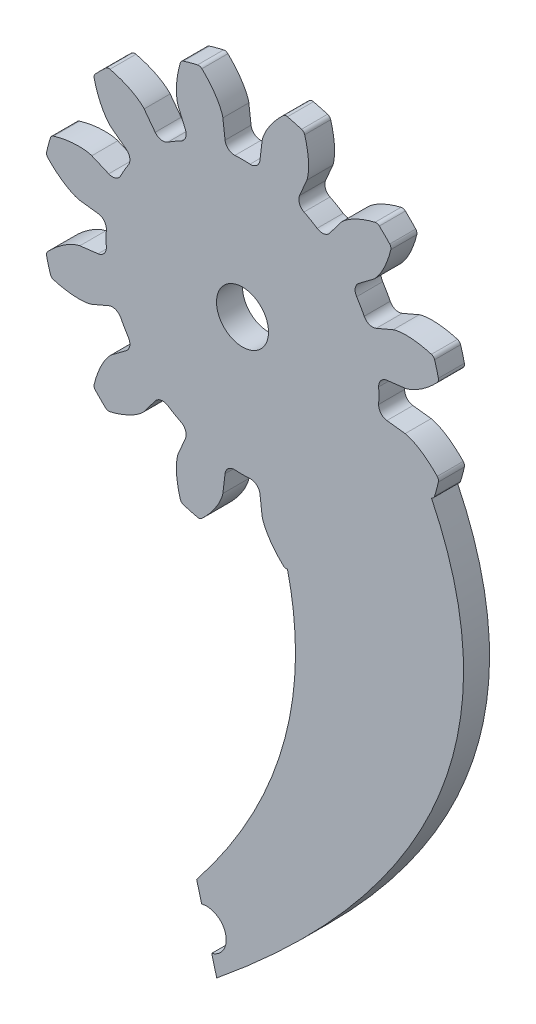
SolidWorks part; units mm, degrees
material "Alloy Steel"
ref_plane "Front" through (0, 0, 0) normal (0, 0, 1) x (1, 0, 0)
ref_plane "Top" through (0, 0, 0) normal (0, 1, 0) x (1, 0, 0)
ref_plane "Right" through (0, 0, 0) normal (1, 0, 0) x (0, 0, -1)
sketch "Sketch1" plane through (0, 0, 0) normal (0, 0, 1) x (1, 0, 0)
  circle A0 centre (0, 0) radius 15.4609
  dimension "OutsideDiameter" = 30.9217
extrude "Boss-Extrude1" add sketch "Sketch1" along normal blind 2
sketch "Sketch3" plane through (0, 0, 0) normal (0, 0, 1) x (1, 0, 0)
  line L0 (0, 0) -> (43.7181, 0) construction
  line L2 (0, 0) -> (-1.2574, 10.4157) construction
  line L3 (0, 0) -> (1.2574, 10.4157) construction
  line L4 (1.2574, 10.4157) -> (1.5105, 12.5127) construction
  line L5 (0, 0) -> (0, 61.276) construction
  line L6 (-1.2574, 10.4157) -> (-1.5105, 12.5127) construction
  circle A0 centre (0, 0) radius 15.4609 construction
  circle A1 centre (0, 0) radius 13.2522 construction
  circle A2 centre (0, 0) radius 12.6036 construction
  arc A3 (1.2574, 10.4157) -> (-1.2574, 10.4157) centre (0, 0) ccw construction
  arc A5 (5.6606, 16.7383) -> (-5.6606, 16.7383) centre (0, 0) ccw
  spline S0 degree 4 poles (-1.5105, 12.5127) (-1.5118, 12.5216) (-1.5159, 12.5465) (-1.526, 12.5932) (-1.5455, 12.6687) (-1.5751, 12.7638) (-1.6185, 12.8852) (-1.6764, 13.026) (-1.7469, 13.1782) (-1.831, 13.3407) (-1.9213, 13.5001) (-2.0172, 13.6562) (-2.118, 13.8091) (-2.2461, 13.9909) (-2.4081, 14.2041) (-2.6093, 14.4459) (-2.8511, 14.711) (-3.1116, 14.9707) (-3.3794, 15.2174) (-3.6624, 15.456) (-3.945, 15.6793) (-4.2506, 15.8995) (-4.5388, 16.0969) (-4.8743, 16.3046) (-5.1487, 16.4683) (-5.5233, 16.6694) (-5.7482, 16.7837) (-6.0156, 16.9122) (-6.1365, 16.9665) (-6.2108, 17) knots 0 0 0 0 0 0.005377 0.015084 0.028532 0.04661 0.064855 0.092111 0.119476 0.146842 0.174209 0.201575 0.228941 0.256307 0.307035 0.361767 0.4165 0.471232 0.525964 0.580697 0.635429 0.690161 0.744894 0.799626 0.854358 0.909091 0.954545 1 1 1 1 1 construction
  spline S1 degree 4 poles (-1.5105, 12.5127) (-1.5118, 12.5216) (-1.5159, 12.5465) (-1.526, 12.5932) (-1.5455, 12.6687) (-1.5751, 12.7638) (-1.6185, 12.8852) (-1.6764, 13.026) (-1.7469, 13.1782) (-1.831, 13.3407) (-1.9213, 13.5001) (-2.0172, 13.6562) (-2.118, 13.8091) (-2.2461, 13.9909) (-2.4081, 14.2041) (-2.6093, 14.4459) (-2.8511, 14.711) (-3.1116, 14.9707) (-3.3794, 15.2174) (-3.6624, 15.456) (-3.945, 15.6793) (-4.2506, 15.8995) (-4.5388, 16.0969) (-4.8743, 16.3046) (-5.1487, 16.4683) (-5.4421, 16.6258) (-5.5863, 16.7008) (-5.6606, 16.7383) knots 0 0 0 0 0 0.005377 0.015084 0.028532 0.04661 0.064855 0.092111 0.119476 0.146842 0.174209 0.201575 0.228941 0.256307 0.307035 0.361767 0.4165 0.471232 0.525964 0.580697 0.635429 0.690161 0.744894 0.799626 0.854358 0.909091 0.909091 0.909091 0.909091 0.909091
  spline S2 degree 4 poles (1.5105, 12.5127) (1.5118, 12.5216) (1.5159, 12.5465) (1.526, 12.5932) (1.5455, 12.6687) (1.5751, 12.7638) (1.6185, 12.8852) (1.6764, 13.026) (1.7469, 13.1782) (1.831, 13.3407) (1.9213, 13.5001) (2.0172, 13.6562) (2.118, 13.8091) (2.2461, 13.9909) (2.4081, 14.2041) (2.6093, 14.4459) (2.8511, 14.711) (3.1116, 14.9707) (3.3794, 15.2174) (3.6624, 15.456) (3.945, 15.6793) (4.2506, 15.8995) (4.5388, 16.0969) (4.8743, 16.3046) (5.1487, 16.4683) (5.5233, 16.6694) (5.7482, 16.7837) (6.0156, 16.9122) (6.1365, 16.9665) (6.2108, 17) knots 0 0 0 0 0 0.005377 0.015084 0.028532 0.04661 0.064855 0.092111 0.119476 0.146842 0.174209 0.201575 0.228941 0.256307 0.307035 0.361767 0.4165 0.471232 0.525964 0.580697 0.635429 0.690161 0.744894 0.799626 0.854358 0.909091 0.954545 1 1 1 1 1 construction
  spline S3 degree 4 poles (1.5105, 12.5127) (1.5118, 12.5216) (1.5159, 12.5465) (1.526, 12.5932) (1.5455, 12.6687) (1.5751, 12.7638) (1.6185, 12.8852) (1.6764, 13.026) (1.7469, 13.1782) (1.831, 13.3407) (1.9213, 13.5001) (2.0172, 13.6562) (2.118, 13.8091) (2.2461, 13.9909) (2.4081, 14.2041) (2.6093, 14.4459) (2.8511, 14.711) (3.1116, 14.9707) (3.3794, 15.2174) (3.6624, 15.456) (3.945, 15.6793) (4.2506, 15.8995) (4.5388, 16.0969) (4.8743, 16.3046) (5.1487, 16.4683) (5.4421, 16.6258) (5.5863, 16.7008) (5.6606, 16.7383) knots 0 0 0 0 0 0.005377 0.015084 0.028532 0.04661 0.064855 0.092111 0.119476 0.146842 0.174209 0.201575 0.228941 0.256307 0.307035 0.361767 0.4165 0.471232 0.525964 0.580697 0.635429 0.690161 0.744894 0.799626 0.854358 0.909091 0.909091 0.909091 0.909091 0.909091
  point P0 (0, 10.4913)
  dimension "OutsideDiameter" = 30.9217
  dimension "PitchCircle" = 26.5043
  dimension "BaseCircle" = 25.2071
  dimension "DedendumCircle" = 20.9826
sketch "DCLTBC" plane through (0, 0, 0) normal (0, 0, 1) x (1, 0, 0)
  line L0 (0, 0) -> (41.04, 0) construction
  line L1 (-1.2574, 10.4157) -> (-1.5105, 12.5127) construction
  line L2 (1.2574, 10.4157) -> (1.5105, 12.5127) construction
  line L3 (-1.2574, 10.4157) -> (-1.5105, 12.5127)
  line L4 (1.2574, 10.4157) -> (1.5105, 12.5127)
  line L5 (0, 0) -> (0, 104.9356) construction
  circle A0 centre (0, 0) radius 15.4609
  circle A1 centre (0, 0) radius 13.2522 construction
  circle A2 centre (0, 0) radius 12.6036 construction
  arc A3 (1.2574, 10.4157) -> (-1.2574, 10.4157) centre (0, 0) ccw construction
  arc A4 (1.2574, 10.4157) -> (-1.2574, 10.4157) centre (0, 0) ccw
  spline S0 degree 4 poles (-993.0276, -117.3129) (-18.3285, 8.2146) (-1.6428, 11.057) (-1.3485, 11.9079) (-1.5455, 12.6687) (-1.5751, 12.7638) (-1.6185, 12.8852) (-1.6764, 13.026) (-1.7469, 13.1782) (-1.831, 13.3407) (-1.9213, 13.5001) (-2.0172, 13.6562) (-2.118, 13.8091) (-2.2461, 13.9909) (-2.4081, 14.2041) (-2.6093, 14.4459) (-2.8511, 14.711) (-3.1116, 14.9707) (-3.3794, 15.2174) (-3.6624, 15.456) (-3.945, 15.6793) (-4.2506, 15.8995) (-4.5388, 16.0969) (-4.8743, 16.3046) (-6.0414, 17.0009) (-9.6339, 18.6454) (22.9818, 1.8118) (-898.4388, 467.1598) knots -0.423011 -0.423011 -0.423011 -0.423011 -0.423011 0.005377 0.015084 0.028532 0.04661 0.064855 0.092111 0.119476 0.146842 0.174209 0.201575 0.228941 0.256307 0.307035 0.361767 0.4165 0.471232 0.525964 0.580697 0.635429 0.690161 0.744894 0.799626 0.854358 1.621262 1.621262 1.621262 1.621262 1.621262 only from (-1.5105, 12.5127) to (-5.6606, 16.7383) construction
  spline S1 degree 4 poles (993.0276, -117.3129) (18.3285, 8.2146) (1.6428, 11.057) (1.3485, 11.9079) (1.5455, 12.6687) (1.5751, 12.7638) (1.6185, 12.8852) (1.6764, 13.026) (1.7469, 13.1782) (1.831, 13.3407) (1.9213, 13.5001) (2.0172, 13.6562) (2.118, 13.8091) (2.2461, 13.9909) (2.4081, 14.2041) (2.6093, 14.4459) (2.8511, 14.711) (3.1116, 14.9707) (3.3794, 15.2174) (3.6624, 15.456) (3.945, 15.6793) (4.2506, 15.8995) (4.5388, 16.0969) (4.8743, 16.3046) (6.0414, 17.0009) (9.6339, 18.6454) (-22.9818, 1.8118) (898.4388, 467.1598) knots -0.423011 -0.423011 -0.423011 -0.423011 -0.423011 0.005377 0.015084 0.028532 0.04661 0.064855 0.092111 0.119476 0.146842 0.174209 0.201575 0.228941 0.256307 0.307035 0.361767 0.4165 0.471232 0.525964 0.580697 0.635429 0.690161 0.744894 0.799626 0.854358 1.621262 1.621262 1.621262 1.621262 1.621262 only from (1.5105, 12.5127) to (5.6606, 16.7383) construction
  spline S2 degree 4 poles (-1.5105, 12.5127) (-1.5118, 12.5216) (-1.5159, 12.5465) (-1.526, 12.5932) (-1.5455, 12.6687) (-1.5751, 12.7638) (-1.6185, 12.8852) (-1.6764, 13.026) (-1.7469, 13.1782) (-1.831, 13.3407) (-1.9213, 13.5001) (-2.0172, 13.6562) (-2.118, 13.8091) (-2.2461, 13.9909) (-2.4081, 14.2041) (-2.6093, 14.4459) (-2.8511, 14.711) (-3.1116, 14.9707) (-3.3794, 15.2174) (-3.6624, 15.456) (-3.945, 15.6793) (-4.2506, 15.8995) (-4.5388, 16.0969) (-4.8743, 16.3046) (-5.1487, 16.4683) (-5.4421, 16.6258) (-5.5863, 16.7008) (-5.6606, 16.7383) knots 0 0 0 0 0 0.005377 0.015084 0.028532 0.04661 0.064855 0.092111 0.119476 0.146842 0.174209 0.201575 0.228941 0.256307 0.307035 0.361767 0.4165 0.471232 0.525964 0.580697 0.635429 0.690161 0.744894 0.799626 0.854358 0.909091 0.909091 0.909091 0.909091 0.909091
  spline S3 degree 4 poles (1.5105, 12.5127) (1.5118, 12.5216) (1.5159, 12.5465) (1.526, 12.5932) (1.5455, 12.6687) (1.5751, 12.7638) (1.6185, 12.8852) (1.6764, 13.026) (1.7469, 13.1782) (1.831, 13.3407) (1.9213, 13.5001) (2.0172, 13.6562) (2.118, 13.8091) (2.2461, 13.9909) (2.4081, 14.2041) (2.6093, 14.4459) (2.8511, 14.711) (3.1116, 14.9707) (3.3794, 15.2174) (3.6624, 15.456) (3.945, 15.6793) (4.2506, 15.8995) (4.5388, 16.0969) (4.8743, 16.3046) (5.1487, 16.4683) (5.4421, 16.6258) (5.5863, 16.7008) (5.6606, 16.7383) knots 0 0 0 0 0 0.005377 0.015084 0.028532 0.04661 0.064855 0.092111 0.119476 0.146842 0.174209 0.201575 0.228941 0.256307 0.307035 0.361767 0.4165 0.471232 0.525964 0.580697 0.635429 0.690161 0.744894 0.799626 0.854358 0.909091 0.909091 0.909091 0.909091 0.909091
  dimension "OutsideDiameter" = 30.9217
  dimension "PitchCircle" = 26.5043
  dimension "BaseCircle" = 25.2071
extrude "Cut-Extrude-DCLTBC" cut sketch "DCLTBC" along normal through all contours L4 S3 A0 S2 L3 A4 region at (0, 13.3393, 0)
fillet "Fillet-Tip-DCLTBC" radius 0.3614 2 edges at (3.2667, 15.1118, 1) (-3.2667, 15.1118, 1)
fillet "Fillet-Root-DCLTBC" radius 0.7228 2 edges at (-1.2574, 10.4157, 1) (1.2574, 10.4157, 1)
pattern_circular "CirPattern-DCLTBC" count 12 over 360 about axis through (0, 0, 2) along (0, 0, 1) of "Cut-Extrude-DCLTBC", "Fillet-Tip-DCLTBC", "Fillet-Root-DCLTBC"
sketch "DCGTBC" [suppressed] plane through (0, 0, 0) normal (0, 0, 1) x (1, 0, 0)
  line L0 (0, 0) -> (41.04, 0) construction
  line L1 (-80.0999, 7.0078) -> (0, 0) construction
  line L2 (0, 0) -> (80.0999, 7.0078) construction
  line L3 (0, 0) -> (-16.5124, 0)
  line L5 (0, 0) -> (0, 104.9356) construction
  circle A0 centre (0, 0) radius 84.1169
  circle A1 centre (0, 0) radius 82.4675 construction
  circle A2 centre (0, 0) radius 74.741 construction
  arc A3 (-1.1471, 80.3977) -> (1.1471, 80.3977) centre (0, 0) ccw construction
  arc A11 (80.0999, 7.0078) -> (-80.0999, 7.0078) centre (0, 0) ccw
  spline S4 degree 4 poles (998.856, 63.0934) (15.4955, 71.3556) (-0.7419, 72.36) (-1.1305, 73.6647) (-1.0562, 74.9951) (-1.0431, 75.1576) (-1.0213, 75.3675) (-0.9896, 75.6147) (-0.9484, 75.8863) (-0.8967, 76.1815) (-0.839, 76.4758) (-0.7758, 76.7691) (-0.7078, 77.0611) (-0.6194, 77.4144) (-0.505, 77.8377) (-0.359, 78.3316) (-0.1792, 78.8907) (0.0195, 79.4594) (0.2277, 80.0179) (0.4526, 80.5809) (0.6804, 81.1247) (0.9319, 81.688) (1.1716, 82.2073) (1.4566, 82.7872) (2.3627, 84.5914) (5.0657, 89.306) (-14.9798, 52.3592) (483.8671, 960.358) knots -0.439653 -0.439653 -0.439653 -0.439653 -0.439653 0.005377 0.015084 0.028532 0.04661 0.064855 0.092111 0.119476 0.146842 0.174209 0.201575 0.228941 0.256307 0.307035 0.361767 0.4165 0.471232 0.525964 0.580697 0.635429 0.690161 0.744894 0.799626 0.854358 1.535039 1.535039 1.535039 1.535039 1.535039 only from (-1.0663, 74.7334) to (2.1399, 84.0897) construction
  spline S5 degree 4 poles (-998.856, 63.0934) (-15.4955, 71.3556) (0.7419, 72.36) (1.1305, 73.6647) (1.0562, 74.9951) (1.0431, 75.1576) (1.0213, 75.3675) (0.9896, 75.6147) (0.9484, 75.8863) (0.8967, 76.1815) (0.839, 76.4758) (0.7758, 76.7691) (0.7078, 77.0611) (0.6194, 77.4144) (0.505, 77.8377) (0.359, 78.3316) (0.1792, 78.8907) (-0.0195, 79.4594) (-0.2277, 80.0179) (-0.4526, 80.5809) (-0.6804, 81.1247) (-0.9319, 81.688) (-1.1716, 82.2073) (-1.4566, 82.7872) (-2.3627, 84.5914) (-5.0657, 89.306) (14.9798, 52.3592) (-483.8671, 960.358) knots -0.439653 -0.439653 -0.439653 -0.439653 -0.439653 0.005377 0.015084 0.028532 0.04661 0.064855 0.092111 0.119476 0.146842 0.174209 0.201575 0.228941 0.256307 0.307035 0.361767 0.4165 0.471232 0.525964 0.580697 0.635429 0.690161 0.744894 0.799626 0.854358 1.535039 1.535039 1.535039 1.535039 1.535039 only from (1.0663, 74.7334) to (-2.1399, 84.0897) construction
  spline S6 degree 4 poles (-1.0663, 74.7334) (-1.0664, 74.7481) (-1.066, 74.7894) (-1.0634, 74.8676) (-1.0562, 74.9951) (-1.0431, 75.1576) (-1.0213, 75.3675) (-0.9896, 75.6147) (-0.9484, 75.8863) (-0.8967, 76.1815) (-0.839, 76.4758) (-0.7758, 76.7691) (-0.7078, 77.0611) (-0.6194, 77.4144) (-0.505, 77.8377) (-0.359, 78.3316) (-0.1792, 78.8907) (0.0195, 79.4594) (0.2277, 80.0179) (0.4526, 80.5809) (0.6804, 81.1247) (0.9319, 81.688) (1.1716, 82.2073) (1.4566, 82.7872) (1.6914, 83.2547) (1.9476, 83.7361) (2.0743, 83.9701) (2.1399, 84.0897) knots 0 0 0 0 0 0.005377 0.015084 0.028532 0.04661 0.064855 0.092111 0.119476 0.146842 0.174209 0.201575 0.228941 0.256307 0.307035 0.361767 0.4165 0.471232 0.525964 0.580697 0.635429 0.690161 0.744894 0.799626 0.854358 0.909091 0.909091 0.909091 0.909091 0.909091
  spline S7 degree 4 poles (1.0663, 74.7334) (1.0664, 74.7481) (1.066, 74.7894) (1.0634, 74.8676) (1.0562, 74.9951) (1.0431, 75.1576) (1.0213, 75.3675) (0.9896, 75.6147) (0.9484, 75.8863) (0.8967, 76.1815) (0.839, 76.4758) (0.7758, 76.7691) (0.7078, 77.0611) (0.6194, 77.4144) (0.505, 77.8377) (0.359, 78.3316) (0.1792, 78.8907) (-0.0195, 79.4594) (-0.2277, 80.0179) (-0.4526, 80.5809) (-0.6804, 81.1247) (-0.9319, 81.688) (-1.1716, 82.2073) (-1.4566, 82.7872) (-1.6914, 83.2547) (-1.9476, 83.7361) (-2.0743, 83.9701) (-2.1399, 84.0897) knots 0 0 0 0 0 0.005377 0.015084 0.028532 0.04661 0.064855 0.092111 0.119476 0.146842 0.174209 0.201575 0.228941 0.256307 0.307035 0.361767 0.4165 0.471232 0.525964 0.580697 0.635429 0.690161 0.744894 0.799626 0.854358 0.909091 0.909091 0.909091 0.909091 0.909091
  dimension "D1" = 5
  dimension "D2" = 5
  dimension "OutsideDiameter" = 30.9217
  dimension "PitchCircle" = 26.5043
  dimension "BaseCircle" = 25.2071
extrude "Cut-Extrude-DCGTBC" [suppressed] cut sketch "DCGTBC" along normal through all
fillet "Fillet-Tip-DCGTBC" [suppressed] radius 0.3614
pattern_circular "CirPattern-DCGTBC" [suppressed] count 12 over 360 of bodies 112
sketch "Sketch5" plane through (0, 0, 2) normal (0, 0, 1) x (1, 0, 0)
  circle A0 centre (0, 0) radius 2
  dimension "D1" = 4
extrude "Cut-Extrude1" cut sketch "Sketch5" against normal up to vertex (2 mm away) up to point (14.9789, 3.1246, 0)
sketch "Sketch8" plane through (0, 0, 2) normal (0, 0, 1) x (1, 0, 0)
  line L24 (7.5645, 10.0811) -> (6.7166, 8.951)
  line L25 (4.3935, 10.2923) -> (4.9482, 11.5916)
  line L26 (1.5105, 12.5127) -> (1.3412, 11.1101)
  line L27 (-1.3412, 11.1101) -> (-1.5105, 12.5127)
  line L28 (-4.9482, 11.5916) -> (-4.3935, 10.2923)
  line L29 (-6.7166, 8.951) -> (-7.5645, 10.0811)
  line L30 (-10.0811, 7.5645) -> (-8.951, 6.7166)
  line L31 (-10.2923, 4.3935) -> (-11.5916, 4.9482)
  line L32 (-12.5127, 1.5105) -> (-11.1101, 1.3412)
  line L33 (-11.1101, -1.3412) -> (-12.5127, -1.5105)
  line L34 (-11.5916, -4.9482) -> (-10.2923, -4.3935)
  line L35 (-8.951, -6.7166) -> (-10.0811, -7.5645)
  line L36 (-7.5645, -10.0811) -> (-6.7166, -8.951)
  line L37 (-4.3935, -10.2923) -> (-4.9482, -11.5916)
  line L38 (-1.5105, -12.5127) -> (-1.3412, -11.1101)
  line L39 (1.3412, -11.1101) -> (1.5105, -12.5127)
  line L40 (4.9482, -11.5916) -> (4.3935, -10.2923)
  line L41 (6.7166, -8.951) -> (7.5645, -10.0811)
  line L42 (10.0811, -7.5645) -> (8.951, -6.7166)
  line L43 (10.2923, -4.3935) -> (11.5916, -4.9482)
  line L44 (12.5127, -1.5105) -> (11.1101, -1.3412)
  line L45 (11.1101, 1.3412) -> (12.5127, 1.5105)
  line L46 (11.5916, 4.9482) -> (10.2923, 4.3935)
  line L47 (8.951, 6.7166) -> (10.0811, 7.5645)
  line L48 (7.5645, 10.0811) -> (6.7166, 8.951)
  line L49 (4.3935, 10.2923) -> (4.9482, 11.5916)
  line L50 (1.5105, 12.5127) -> (1.3412, 11.1101)
  line L51 (-1.3412, 11.1101) -> (-1.5105, 12.5127)
  line L52 (-4.9482, 11.5916) -> (-4.3935, 10.2923)
  line L53 (-6.7166, 8.951) -> (-7.5645, 10.0811)
  line L54 (-10.0811, 7.5645) -> (-8.951, 6.7166)
  line L55 (-10.2923, 4.3935) -> (-11.5916, 4.9482)
  line L56 (-12.5127, 1.5105) -> (-11.1101, 1.3412)
  line L57 (-11.1101, -1.3412) -> (-12.5127, -1.5105)
  line L58 (-11.5916, -4.9482) -> (-10.2923, -4.3935)
  line L59 (-8.951, -6.7166) -> (-10.0811, -7.5645)
  line L60 (-7.5645, -10.0811) -> (-6.7166, -8.951)
  line L61 (-4.3935, -10.2923) -> (-4.9482, -11.5916)
  line L62 (-1.5105, -12.5127) -> (-1.3412, -11.1101)
  line L63 (1.3412, -11.1101) -> (1.5105, -12.5127)
  line L64 (4.9482, -11.5916) -> (4.3935, -10.2923)
  line L65 (6.7166, -8.951) -> (7.5645, -10.0811)
  line L66 (10.0811, -7.5645) -> (8.951, -6.7166)
  line L67 (10.2923, -4.3935) -> (11.5916, -4.9482)
  line L68 (12.5127, -1.5105) -> (11.1101, -1.3412)
  line L69 (11.1101, 1.3412) -> (12.5127, 1.5105)
  line L70 (11.5916, 4.9482) -> (10.2923, 4.3935)
  line L71 (8.951, 6.7166) -> (10.0811, 7.5645)
  arc A72 (11.3234, 10.5271) -> (10.5271, 11.3234) centre (0, 0) ccw
  arc A73 (10.5271, 11.3234) -> (10.1954, 11.4098) centre (10.281, 11.0587) ccw
  arc A74 (5.7428, 8.78) -> (6.7166, 8.951) centre (6.1385, 9.3849) ccw
  arc A75 (5.7428, 8.78) -> (4.7323, 9.3634) centre (0, 0) ccw
  arc A76 (4.3935, 10.2923) -> (4.7323, 9.3634) centre (5.0583, 10.0085) ccw
  arc A77 (4.7835, 14.5344) -> (4.5428, 14.7784) centre (4.4366, 14.433) ccw
  arc A78 (4.5428, 14.7784) -> (3.455, 15.0699) centre (0, 0) ccw
  arc A79 (3.455, 15.0699) -> (3.1246, 14.9789) centre (3.3742, 14.7176) ccw
  arc A80 (0.5834, 10.4751) -> (1.3412, 11.1101) centre (0.6236, 11.1968) ccw
  arc A81 (0.5834, 10.4751) -> (-0.5834, 10.4751) centre (0, 0) ccw
  arc A82 (-1.3412, 11.1101) -> (-0.5834, 10.4751) centre (-0.6236, 11.1968) ccw
  arc A83 (-3.1246, 14.9789) -> (-3.455, 15.0699) centre (-3.3742, 14.7176) ccw
  arc A84 (-3.455, 15.0699) -> (-4.5428, 14.7784) centre (0, 0) ccw
  arc A85 (-4.5428, 14.7784) -> (-4.7835, 14.5344) centre (-4.4366, 14.433) ccw
  arc A86 (-4.7323, 9.3634) -> (-4.3935, 10.2923) centre (-5.0583, 10.0085) ccw
  arc A87 (-4.7323, 9.3634) -> (-5.7428, 8.78) centre (0, 0) ccw
  arc A88 (-6.7166, 8.951) -> (-5.7428, 8.78) centre (-6.1385, 9.3849) ccw
  arc A89 (-10.1954, 11.4098) -> (-10.5271, 11.3234) centre (-10.281, 11.0587) ccw
  arc A90 (-10.5271, 11.3234) -> (-11.3234, 10.5271) centre (0, 0) ccw
  arc A91 (-11.3234, 10.5271) -> (-11.4098, 10.1954) centre (-11.0587, 10.281) ccw
  arc A92 (-8.78, 5.7428) -> (-8.951, 6.7166) centre (-9.3849, 6.1385) ccw
  arc A93 (-8.78, 5.7428) -> (-9.3634, 4.7323) centre (0, 0) ccw
  arc A94 (-10.2923, 4.3935) -> (-9.3634, 4.7323) centre (-10.0085, 5.0583) ccw
  arc A95 (-14.5344, 4.7835) -> (-14.7784, 4.5428) centre (-14.433, 4.4366) ccw
  arc A96 (-14.7784, 4.5428) -> (-15.0699, 3.455) centre (0, 0) ccw
  arc A97 (-15.0699, 3.455) -> (-14.9789, 3.1246) centre (-14.7176, 3.3742) ccw
  arc A98 (-10.4751, 0.5834) -> (-11.1101, 1.3412) centre (-11.1968, 0.6236) ccw
  arc A99 (-10.4751, 0.5834) -> (-10.4751, -0.5834) centre (0, 0) ccw
  arc A100 (-11.1101, -1.3412) -> (-10.4751, -0.5834) centre (-11.1968, -0.6236) ccw
  arc A101 (-14.9789, -3.1246) -> (-15.0699, -3.455) centre (-14.7176, -3.3742) ccw
  arc A102 (-15.0699, -3.455) -> (-14.7784, -4.5428) centre (0, 0) ccw
  arc A103 (-14.7784, -4.5428) -> (-14.5344, -4.7835) centre (-14.433, -4.4366) ccw
  arc A104 (-9.3634, -4.7323) -> (-10.2923, -4.3935) centre (-10.0085, -5.0583) ccw
  arc A105 (-9.3634, -4.7323) -> (-8.78, -5.7428) centre (0, 0) ccw
  arc A106 (-8.951, -6.7166) -> (-8.78, -5.7428) centre (-9.3849, -6.1385) ccw
  arc A107 (-11.4098, -10.1954) -> (-11.3234, -10.5271) centre (-11.0587, -10.281) ccw
  arc A108 (-11.3234, -10.5271) -> (-10.5271, -11.3234) centre (0, 0) ccw
  arc A109 (-10.5271, -11.3234) -> (-10.1954, -11.4098) centre (-10.281, -11.0587) ccw
  arc A110 (-5.7428, -8.78) -> (-6.7166, -8.951) centre (-6.1385, -9.3849) ccw
  arc A111 (-5.7428, -8.78) -> (-4.7323, -9.3634) centre (0, 0) ccw
  arc A112 (-4.3935, -10.2923) -> (-4.7323, -9.3634) centre (-5.0583, -10.0085) ccw
  arc A113 (-4.7835, -14.5344) -> (-4.5428, -14.7784) centre (-4.4366, -14.433) ccw
  arc A114 (-4.5428, -14.7784) -> (-3.455, -15.0699) centre (0, 0) ccw
  arc A115 (-3.455, -15.0699) -> (-3.1246, -14.9789) centre (-3.3742, -14.7176) ccw
  arc A116 (-0.5834, -10.4751) -> (-1.3412, -11.1101) centre (-0.6236, -11.1968) ccw
  arc A117 (-0.5834, -10.4751) -> (0.5834, -10.4751) centre (0, 0) ccw
  arc A118 (1.3412, -11.1101) -> (0.5834, -10.4751) centre (0.6236, -11.1968) ccw
  arc A119 (3.1246, -14.9789) -> (3.455, -15.0699) centre (3.3742, -14.7176) ccw
  arc A120 (3.455, -15.0699) -> (4.5428, -14.7784) centre (0, 0) ccw
  arc A121 (4.5428, -14.7784) -> (4.7835, -14.5344) centre (4.4366, -14.433) ccw
  arc A122 (4.7323, -9.3634) -> (4.3935, -10.2923) centre (5.0583, -10.0085) ccw
  arc A123 (4.7323, -9.3634) -> (5.7428, -8.78) centre (0, 0) ccw
  arc A124 (6.7166, -8.951) -> (5.7428, -8.78) centre (6.1385, -9.3849) ccw
  arc A125 (10.1954, -11.4098) -> (10.5271, -11.3234) centre (10.281, -11.0587) ccw
  arc A126 (10.5271, -11.3234) -> (11.3234, -10.5271) centre (0, 0) ccw
  arc A127 (11.3234, -10.5271) -> (11.4098, -10.1954) centre (11.0587, -10.281) ccw
  arc A128 (8.78, -5.7428) -> (8.951, -6.7166) centre (9.3849, -6.1385) ccw
  arc A129 (8.78, -5.7428) -> (9.3634, -4.7323) centre (0, 0) ccw
  arc A130 (10.2923, -4.3935) -> (9.3634, -4.7323) centre (10.0085, -5.0583) ccw
  arc A131 (14.5344, -4.7835) -> (14.7784, -4.5428) centre (14.433, -4.4366) ccw
  arc A132 (14.7784, -4.5428) -> (15.0699, -3.455) centre (0, 0) ccw
  arc A133 (15.0699, -3.455) -> (14.9789, -3.1246) centre (14.7176, -3.3742) ccw
  arc A134 (10.4751, -0.5834) -> (11.1101, -1.3412) centre (11.1968, -0.6236) ccw
  arc A135 (10.4751, -0.5834) -> (10.4751, 0.5834) centre (0, 0) ccw
  arc A136 (11.1101, 1.3412) -> (10.4751, 0.5834) centre (11.1968, 0.6236) ccw
  arc A137 (14.9789, 3.1246) -> (15.0699, 3.455) centre (14.7176, 3.3742) ccw
  arc A138 (15.0699, 3.455) -> (14.7784, 4.5428) centre (0, 0) ccw
  arc A139 (14.7784, 4.5428) -> (14.5344, 4.7835) centre (14.433, 4.4366) ccw
  arc A140 (9.3634, 4.7323) -> (10.2923, 4.3935) centre (10.0085, 5.0583) ccw
  arc A141 (9.3634, 4.7323) -> (8.78, 5.7428) centre (0, 0) ccw
  arc A142 (8.951, 6.7166) -> (8.78, 5.7428) centre (9.3849, 6.1385) ccw
  arc A143 (11.4098, 10.1954) -> (11.3234, 10.5271) centre (11.0587, 10.281) ccw
  arc A144 (11.3234, 10.5271) -> (10.5271, 11.3234) centre (0, 0) ccw
  arc A145 (10.5271, 11.3234) -> (10.1954, 11.4098) centre (10.281, 11.0587) ccw
  arc A146 (5.7428, 8.78) -> (6.7166, 8.951) centre (6.1385, 9.3849) ccw
  arc A147 (5.7428, 8.78) -> (4.7323, 9.3634) centre (0, 0) ccw
  arc A148 (4.3935, 10.2923) -> (4.7323, 9.3634) centre (5.0583, 10.0085) ccw
  arc A149 (4.7835, 14.5344) -> (4.5428, 14.7784) centre (4.4366, 14.433) ccw
  arc A150 (4.5428, 14.7784) -> (3.455, 15.0699) centre (0, 0) ccw
  arc A151 (3.455, 15.0699) -> (3.1246, 14.9789) centre (3.3742, 14.7176) ccw
  arc A152 (0.5834, 10.4751) -> (1.3412, 11.1101) centre (0.6236, 11.1968) ccw
  arc A153 (0.5834, 10.4751) -> (-0.5834, 10.4751) centre (0, 0) ccw
  arc A154 (-1.3412, 11.1101) -> (-0.5834, 10.4751) centre (-0.6236, 11.1968) ccw
  arc A155 (-3.1246, 14.9789) -> (-3.455, 15.0699) centre (-3.3742, 14.7176) ccw
  arc A156 (-3.455, 15.0699) -> (-4.5428, 14.7784) centre (0, 0) ccw
  arc A157 (-4.5428, 14.7784) -> (-4.7835, 14.5344) centre (-4.4366, 14.433) ccw
  arc A158 (-4.7323, 9.3634) -> (-4.3935, 10.2923) centre (-5.0583, 10.0085) ccw
  arc A159 (-4.7323, 9.3634) -> (-5.7428, 8.78) centre (0, 0) ccw
  arc A160 (-6.7166, 8.951) -> (-5.7428, 8.78) centre (-6.1385, 9.3849) ccw
  arc A161 (-10.1954, 11.4098) -> (-10.5271, 11.3234) centre (-10.281, 11.0587) ccw
  arc A162 (-10.5271, 11.3234) -> (-11.3234, 10.5271) centre (0, 0) ccw
  arc A163 (-11.3234, 10.5271) -> (-11.4098, 10.1954) centre (-11.0587, 10.281) ccw
  arc A164 (-8.78, 5.7428) -> (-8.951, 6.7166) centre (-9.3849, 6.1385) ccw
  arc A165 (-8.78, 5.7428) -> (-9.3634, 4.7323) centre (0, 0) ccw
  arc A166 (-10.2923, 4.3935) -> (-9.3634, 4.7323) centre (-10.0085, 5.0583) ccw
  arc A167 (-14.5344, 4.7835) -> (-14.7784, 4.5428) centre (-14.433, 4.4366) ccw
  arc A168 (-14.7784, 4.5428) -> (-15.0699, 3.455) centre (0, 0) ccw
  arc A169 (-15.0699, 3.455) -> (-14.9789, 3.1246) centre (-14.7176, 3.3742) ccw
  arc A170 (-10.4751, 0.5834) -> (-11.1101, 1.3412) centre (-11.1968, 0.6236) ccw
  arc A171 (-10.4751, 0.5834) -> (-10.4751, -0.5834) centre (0, 0) ccw
  arc A172 (-11.1101, -1.3412) -> (-10.4751, -0.5834) centre (-11.1968, -0.6236) ccw
  arc A173 (-14.9789, -3.1246) -> (-15.0699, -3.455) centre (-14.7176, -3.3742) ccw
  arc A174 (-15.0699, -3.455) -> (-14.7784, -4.5428) centre (0, 0) ccw
  arc A175 (-14.7784, -4.5428) -> (-14.5344, -4.7835) centre (-14.433, -4.4366) ccw
  arc A176 (-9.3634, -4.7323) -> (-10.2923, -4.3935) centre (-10.0085, -5.0583) ccw
  arc A177 (-9.3634, -4.7323) -> (-8.78, -5.7428) centre (0, 0) ccw
  arc A178 (-8.951, -6.7166) -> (-8.78, -5.7428) centre (-9.3849, -6.1385) ccw
  arc A179 (-11.4098, -10.1954) -> (-11.3234, -10.5271) centre (-11.0587, -10.281) ccw
  arc A180 (-11.3234, -10.5271) -> (-10.5271, -11.3234) centre (0, 0) ccw
  arc A181 (-10.5271, -11.3234) -> (-10.1954, -11.4098) centre (-10.281, -11.0587) ccw
  arc A182 (-5.7428, -8.78) -> (-6.7166, -8.951) centre (-6.1385, -9.3849) ccw
  arc A183 (-5.7428, -8.78) -> (-4.7323, -9.3634) centre (0, 0) ccw
  arc A184 (-4.3935, -10.2923) -> (-4.7323, -9.3634) centre (-5.0583, -10.0085) ccw
  arc A185 (-4.7835, -14.5344) -> (-4.5428, -14.7784) centre (-4.4366, -14.433) ccw
  arc A186 (-4.5428, -14.7784) -> (-3.455, -15.0699) centre (0, 0) ccw
  arc A187 (-3.455, -15.0699) -> (-3.1246, -14.9789) centre (-3.3742, -14.7176) ccw
  arc A188 (-0.5834, -10.4751) -> (-1.3412, -11.1101) centre (-0.6236, -11.1968) ccw
  arc A189 (-0.5834, -10.4751) -> (0.5834, -10.4751) centre (0, 0) ccw
  arc A190 (1.3412, -11.1101) -> (0.5834, -10.4751) centre (0.6236, -11.1968) ccw
  arc A191 (3.1246, -14.9789) -> (3.455, -15.0699) centre (3.3742, -14.7176) ccw
  arc A192 (3.455, -15.0699) -> (4.5428, -14.7784) centre (0, 0) ccw
  arc A193 (4.5428, -14.7784) -> (4.7835, -14.5344) centre (4.4366, -14.433) ccw
  arc A194 (4.7323, -9.3634) -> (4.3935, -10.2923) centre (5.0583, -10.0085) ccw
  arc A195 (4.7323, -9.3634) -> (5.7428, -8.78) centre (0, 0) ccw
  arc A196 (6.7166, -8.951) -> (5.7428, -8.78) centre (6.1385, -9.3849) ccw
  arc A197 (10.1954, -11.4098) -> (10.5271, -11.3234) centre (10.281, -11.0587) ccw
  arc A198 (10.5271, -11.3234) -> (11.3234, -10.5271) centre (0, 0) ccw
  arc A199 (11.3234, -10.5271) -> (11.4098, -10.1954) centre (11.0587, -10.281) ccw
  arc A200 (8.78, -5.7428) -> (8.951, -6.7166) centre (9.3849, -6.1385) ccw
  arc A201 (8.78, -5.7428) -> (9.3634, -4.7323) centre (0, 0) ccw
  arc A202 (10.2923, -4.3935) -> (9.3634, -4.7323) centre (10.0085, -5.0583) ccw
  arc A203 (14.5344, -4.7835) -> (14.7784, -4.5428) centre (14.433, -4.4366) ccw
  arc A204 (14.7784, -4.5428) -> (15.0699, -3.455) centre (0, 0) ccw
  arc A205 (15.0699, -3.455) -> (14.9789, -3.1246) centre (14.7176, -3.3742) ccw
  arc A206 (10.4751, -0.5834) -> (11.1101, -1.3412) centre (11.1968, -0.6236) ccw
  arc A207 (10.4751, -0.5834) -> (10.4751, 0.5834) centre (0, 0) ccw
  arc A208 (11.1101, 1.3412) -> (10.4751, 0.5834) centre (11.1968, 0.6236) ccw
  arc A209 (14.9789, 3.1246) -> (15.0699, 3.455) centre (14.7176, 3.3742) ccw
  arc A210 (15.0699, 3.455) -> (14.7784, 4.5428) centre (0, 0) ccw
  arc A211 (14.7784, 4.5428) -> (14.5344, 4.7835) centre (14.433, 4.4366) ccw
  arc A212 (9.3634, 4.7323) -> (10.2923, 4.3935) centre (10.0085, 5.0583) ccw
  arc A213 (9.3634, 4.7323) -> (8.78, 5.7428) centre (0, 0) ccw
  arc A214 (8.951, 6.7166) -> (8.78, 5.7428) centre (9.3849, 6.1385) ccw
  arc A215 (11.4098, 10.1954) -> (11.3234, 10.5271) centre (11.0587, 10.281) ccw
  spline S24 degree 4 poles (3004.3949, -173.0999) (-5.6391, 11.2899) (19.2697, 10.8199) (13.7342, 12.5566) (9.4827, 11.2059) (9.1876, 11.0971) (8.9407, 10.9934) (8.7388, 10.9) (8.5751, 10.818) (8.4139, 10.7308) (8.2561, 10.6379) (8.102, 10.5391) (7.9648, 10.4426) (7.8443, 10.3496) (7.746, 10.2662) (7.6728, 10.1987) (6.9601, 9.474) (6.8805, 8.1826) (36.5833, -15.491) (2391.63, -1810.6545) knots -2.482238 -2.482238 -2.482238 -2.482238 -2.482238 0.02973 0.084463 0.139195 0.189923 0.217289 0.244655 0.272021 0.299388 0.326754 0.35412 0.381375 0.39962 0.417698 0.431146 0.440853 1.00699 1.00699 1.00699 1.00699 1.00699 only from (10.1954, 11.4098) to (7.5645, 10.0811)
  spline S25 degree 4 poles (-2763.9006, 1165.8904) (-31.7074, 23.9366) (3.6461, 10.05) (4.7246, 10.7647) (4.9959, 11.7442) (5.0178, 11.8413) (5.0409, 11.9681) (5.0612, 12.119) (5.0762, 12.2861) (5.0847, 12.4689) (5.0862, 12.6521) (5.0812, 12.8353) (5.0703, 13.018) (5.0502, 13.2395) (5.0166, 13.5052) (4.9633, 13.8152) (4.0073, 18.1725) (-0.2645, 22.098) (12.5968, 0.7615) (-1652.0934, 2515.3127) knots -0.560761 -0.560761 -0.560761 -0.560761 -0.560761 0.005377 0.015084 0.028532 0.04661 0.064855 0.092111 0.119476 0.146842 0.174209 0.201575 0.228941 0.256307 0.307035 0.361767 0.4165 2.928463 2.928463 2.928463 2.928463 2.928463 only from (4.9482, 11.5916) to (4.7835, 14.5344)
  spline S26 degree 4 poles (2688.4323, 1352.2885) (-10.5286, 6.9578) (11.2781, 19.0052) (5.6159, 17.7414) (2.6093, 14.4459) (2.4081, 14.2041) (2.2461, 13.9909) (2.118, 13.8091) (2.0172, 13.6562) (1.9213, 13.5001) (1.831, 13.3407) (1.7469, 13.1782) (1.6764, 13.026) (1.6185, 12.8852) (1.5751, 12.7638) (1.5455, 12.6687) (1.2907, 11.6848) (1.8674, 10.5266) (39.4276, 4.876) (2976.5396, -372.2578) knots -2.482238 -2.482238 -2.482238 -2.482238 -2.482238 0.02973 0.084463 0.139195 0.189923 0.217289 0.244655 0.272021 0.299388 0.326754 0.35412 0.381375 0.39962 0.417698 0.431146 0.440853 1.00699 1.00699 1.00699 1.00699 1.00699 only from (3.1246, 14.9789) to (1.5105, 12.5127)
  spline S27 degree 4 poles (-2976.5533, -372.2595) (-39.4277, 4.876) (-1.8674, 10.5266) (-1.2907, 11.6848) (-1.5455, 12.6687) (-1.5751, 12.7638) (-1.6185, 12.8852) (-1.6764, 13.026) (-1.7469, 13.1782) (-1.831, 13.3407) (-1.9213, 13.5001) (-2.0172, 13.6562) (-2.118, 13.8091) (-2.2461, 13.9909) (-2.4081, 14.2041) (-2.6093, 14.4459) (-5.6158, 17.7414) (-11.2781, 19.0052) (10.5284, 6.9579) (-2688.4111, 1352.278) knots -0.560761 -0.560761 -0.560761 -0.560761 -0.560761 0.005377 0.015084 0.028532 0.04661 0.064855 0.092111 0.119476 0.146842 0.174209 0.201575 0.228941 0.256307 0.307035 0.361767 0.4165 2.928463 2.928463 2.928463 2.928463 2.928463 only from (-1.5105, 12.5127) to (-3.1246, 14.9789)
  spline S28 degree 4 poles (1652.1064, 2515.3324) (-12.5969, 0.7613) (0.2645, 22.098) (-4.0073, 18.1725) (-4.9633, 13.8152) (-5.0166, 13.5052) (-5.0502, 13.2395) (-5.0703, 13.018) (-5.0812, 12.8353) (-5.0862, 12.6521) (-5.0847, 12.4689) (-5.0762, 12.2861) (-5.0612, 12.119) (-5.0409, 11.9681) (-5.0178, 11.8413) (-4.9959, 11.7442) (-4.7246, 10.7647) (-3.6461, 10.05) (31.7073, 23.9366) (2763.8878, 1165.8851) knots -2.482238 -2.482238 -2.482238 -2.482238 -2.482238 0.02973 0.084463 0.139195 0.189923 0.217289 0.244655 0.272021 0.299388 0.326754 0.35412 0.381375 0.39962 0.417698 0.431146 0.440853 1.00699 1.00699 1.00699 1.00699 1.00699 only from (-4.7835, 14.5344) to (-4.9482, 11.5916)
  spline S29 degree 4 poles (-2391.641, -1810.6629) (-36.5834, -15.4911) (-6.8805, 8.1826) (-6.9601, 9.474) (-7.6728, 10.1987) (-7.746, 10.2662) (-7.8443, 10.3496) (-7.9648, 10.4426) (-8.102, 10.5391) (-8.2561, 10.6379) (-8.4139, 10.7308) (-8.5751, 10.818) (-8.7388, 10.9) (-8.9407, 10.9934) (-9.1876, 11.0971) (-9.4827, 11.2059) (-13.7342, 12.5566) (-19.2697, 10.8199) (5.639, 11.2899) (-3004.3713, -173.0985) knots -0.560761 -0.560761 -0.560761 -0.560761 -0.560761 0.005377 0.015084 0.028532 0.04661 0.064855 0.092111 0.119476 0.146842 0.174209 0.201575 0.228941 0.256307 0.307035 0.361767 0.4165 2.928463 2.928463 2.928463 2.928463 2.928463 only from (-7.5645, 10.0811) to (-10.1954, 11.4098)
  spline S30 degree 4 poles (173.0999, 3004.3949) (-11.2899, -5.6391) (-10.8199, 19.2697) (-12.5566, 13.7342) (-11.2059, 9.4827) (-11.0971, 9.1876) (-10.9934, 8.9407) (-10.9, 8.7388) (-10.818, 8.5751) (-10.7308, 8.4139) (-10.6379, 8.2561) (-10.5391, 8.102) (-10.4426, 7.9648) (-10.3496, 7.8443) (-10.2662, 7.746) (-10.1987, 7.6728) (-9.474, 6.9601) (-8.1826, 6.8805) (15.491, 36.5833) (1810.6545, 2391.63) knots -2.482238 -2.482238 -2.482238 -2.482238 -2.482238 0.02973 0.084463 0.139195 0.189923 0.217289 0.244655 0.272021 0.299388 0.326754 0.35412 0.381375 0.39962 0.417698 0.431146 0.440853 1.00699 1.00699 1.00699 1.00699 1.00699 only from (-11.4098, 10.1954) to (-10.0811, 7.5645)
  spline S31 degree 4 poles (-1165.8904, -2763.9006) (-23.9366, -31.7074) (-10.05, 3.6461) (-10.7647, 4.7246) (-11.7442, 4.9959) (-11.8413, 5.0178) (-11.9681, 5.0409) (-12.119, 5.0612) (-12.2861, 5.0762) (-12.4689, 5.0847) (-12.6521, 5.0862) (-12.8353, 5.0812) (-13.018, 5.0703) (-13.2395, 5.0502) (-13.5052, 5.0166) (-13.8152, 4.9633) (-18.1725, 4.0073) (-22.098, -0.2645) (-0.7615, 12.5968) (-2515.3127, -1652.0934) knots -0.560761 -0.560761 -0.560761 -0.560761 -0.560761 0.005377 0.015084 0.028532 0.04661 0.064855 0.092111 0.119476 0.146842 0.174209 0.201575 0.228941 0.256307 0.307035 0.361767 0.4165 2.928463 2.928463 2.928463 2.928463 2.928463 only from (-11.5916, 4.9482) to (-14.5344, 4.7835)
  spline S32 degree 4 poles (-1352.2885, 2688.4323) (-6.9578, -10.5286) (-19.0052, 11.2781) (-17.7414, 5.6159) (-14.4459, 2.6093) (-14.2041, 2.4081) (-13.9909, 2.2461) (-13.8091, 2.118) (-13.6562, 2.0172) (-13.5001, 1.9213) (-13.3407, 1.831) (-13.1782, 1.7469) (-13.026, 1.6764) (-12.8852, 1.6185) (-12.7638, 1.5751) (-12.6687, 1.5455) (-11.6848, 1.2907) (-10.5266, 1.8674) (-4.876, 39.4276) (372.2578, 2976.5396) knots -2.482238 -2.482238 -2.482238 -2.482238 -2.482238 0.02973 0.084463 0.139195 0.189923 0.217289 0.244655 0.272021 0.299388 0.326754 0.35412 0.381375 0.39962 0.417698 0.431146 0.440853 1.00699 1.00699 1.00699 1.00699 1.00699 only from (-14.9789, 3.1246) to (-12.5127, 1.5105)
  spline S33 degree 4 poles (372.2595, -2976.5533) (-4.876, -39.4277) (-10.5266, -1.8674) (-11.6848, -1.2907) (-12.6687, -1.5455) (-12.7638, -1.5751) (-12.8852, -1.6185) (-13.026, -1.6764) (-13.1782, -1.7469) (-13.3407, -1.831) (-13.5001, -1.9213) (-13.6562, -2.0172) (-13.8091, -2.118) (-13.9909, -2.2461) (-14.2041, -2.4081) (-14.4459, -2.6093) (-17.7414, -5.6158) (-19.0052, -11.2781) (-6.9579, 10.5284) (-1352.278, -2688.4111) knots -0.560761 -0.560761 -0.560761 -0.560761 -0.560761 0.005377 0.015084 0.028532 0.04661 0.064855 0.092111 0.119476 0.146842 0.174209 0.201575 0.228941 0.256307 0.307035 0.361767 0.4165 2.928463 2.928463 2.928463 2.928463 2.928463 only from (-12.5127, -1.5105) to (-14.9789, -3.1246)
  spline S34 degree 4 poles (-2515.3324, 1652.1064) (-0.7613, -12.5969) (-22.098, 0.2645) (-18.1725, -4.0073) (-13.8152, -4.9633) (-13.5052, -5.0166) (-13.2395, -5.0502) (-13.018, -5.0703) (-12.8353, -5.0812) (-12.6521, -5.0862) (-12.4689, -5.0847) (-12.2861, -5.0762) (-12.119, -5.0612) (-11.9681, -5.0409) (-11.8413, -5.0178) (-11.7442, -4.9959) (-10.7647, -4.7246) (-10.05, -3.6461) (-23.9366, 31.7073) (-1165.8851, 2763.8878) knots -2.482238 -2.482238 -2.482238 -2.482238 -2.482238 0.02973 0.084463 0.139195 0.189923 0.217289 0.244655 0.272021 0.299388 0.326754 0.35412 0.381375 0.39962 0.417698 0.431146 0.440853 1.00699 1.00699 1.00699 1.00699 1.00699 only from (-14.5344, -4.7835) to (-11.5916, -4.9482)
  spline S35 degree 4 poles (1810.6629, -2391.641) (15.4911, -36.5834) (-8.1826, -6.8805) (-9.474, -6.9601) (-10.1987, -7.6728) (-10.2662, -7.746) (-10.3496, -7.8443) (-10.4426, -7.9648) (-10.5391, -8.102) (-10.6379, -8.2561) (-10.7308, -8.4139) (-10.818, -8.5751) (-10.9, -8.7388) (-10.9934, -8.9407) (-11.0971, -9.1876) (-11.2059, -9.4827) (-12.5566, -13.7342) (-10.8199, -19.2697) (-11.2899, 5.639) (173.0985, -3004.3713) knots -0.560761 -0.560761 -0.560761 -0.560761 -0.560761 0.005377 0.015084 0.028532 0.04661 0.064855 0.092111 0.119476 0.146842 0.174209 0.201575 0.228941 0.256307 0.307035 0.361767 0.4165 2.928463 2.928463 2.928463 2.928463 2.928463 only from (-10.0811, -7.5645) to (-11.4098, -10.1954)
  spline S36 degree 4 poles (-3004.3949, 173.0999) (5.6391, -11.2899) (-19.2697, -10.8199) (-13.7342, -12.5566) (-9.4827, -11.2059) (-9.1876, -11.0971) (-8.9407, -10.9934) (-8.7388, -10.9) (-8.5751, -10.818) (-8.4139, -10.7308) (-8.2561, -10.6379) (-8.102, -10.5391) (-7.9648, -10.4426) (-7.8443, -10.3496) (-7.746, -10.2662) (-7.6728, -10.1987) (-6.9601, -9.474) (-6.8805, -8.1826) (-36.5833, 15.491) (-2391.63, 1810.6545) knots -2.482238 -2.482238 -2.482238 -2.482238 -2.482238 0.02973 0.084463 0.139195 0.189923 0.217289 0.244655 0.272021 0.299388 0.326754 0.35412 0.381375 0.39962 0.417698 0.431146 0.440853 1.00699 1.00699 1.00699 1.00699 1.00699 only from (-10.1954, -11.4098) to (-7.5645, -10.0811)
  spline S37 degree 4 poles (2763.9006, -1165.8904) (31.7074, -23.9366) (-3.6461, -10.05) (-4.7246, -10.7647) (-4.9959, -11.7442) (-5.0178, -11.8413) (-5.0409, -11.9681) (-5.0612, -12.119) (-5.0762, -12.2861) (-5.0847, -12.4689) (-5.0862, -12.6521) (-5.0812, -12.8353) (-5.0703, -13.018) (-5.0502, -13.2395) (-5.0166, -13.5052) (-4.9633, -13.8152) (-4.0073, -18.1725) (0.2645, -22.098) (-12.5968, -0.7615) (1652.0934, -2515.3127) knots -0.560761 -0.560761 -0.560761 -0.560761 -0.560761 0.005377 0.015084 0.028532 0.04661 0.064855 0.092111 0.119476 0.146842 0.174209 0.201575 0.228941 0.256307 0.307035 0.361767 0.4165 2.928463 2.928463 2.928463 2.928463 2.928463 only from (-4.9482, -11.5916) to (-4.7835, -14.5344)
  spline S38 degree 4 poles (-2688.4323, -1352.2885) (10.5286, -6.9578) (-11.2781, -19.0052) (-5.6159, -17.7414) (-2.6093, -14.4459) (-2.4081, -14.2041) (-2.2461, -13.9909) (-2.118, -13.8091) (-2.0172, -13.6562) (-1.9213, -13.5001) (-1.831, -13.3407) (-1.7469, -13.1782) (-1.6764, -13.026) (-1.6185, -12.8852) (-1.5751, -12.7638) (-1.5455, -12.6687) (-1.2907, -11.6848) (-1.8674, -10.5266) (-39.4276, -4.876) (-2976.5396, 372.2578) knots -2.482238 -2.482238 -2.482238 -2.482238 -2.482238 0.02973 0.084463 0.139195 0.189923 0.217289 0.244655 0.272021 0.299388 0.326754 0.35412 0.381375 0.39962 0.417698 0.431146 0.440853 1.00699 1.00699 1.00699 1.00699 1.00699 only from (-3.1246, -14.9789) to (-1.5105, -12.5127)
  spline S39 degree 4 poles (2976.5533, 372.2595) (39.4277, -4.876) (1.8674, -10.5266) (1.2907, -11.6848) (1.5455, -12.6687) (1.5751, -12.7638) (1.6185, -12.8852) (1.6764, -13.026) (1.7469, -13.1782) (1.831, -13.3407) (1.9213, -13.5001) (2.0172, -13.6562) (2.118, -13.8091) (2.2461, -13.9909) (2.4081, -14.2041) (2.6093, -14.4459) (5.6158, -17.7414) (11.2781, -19.0052) (-10.5284, -6.9579) (2688.4111, -1352.278) knots -0.560761 -0.560761 -0.560761 -0.560761 -0.560761 0.005377 0.015084 0.028532 0.04661 0.064855 0.092111 0.119476 0.146842 0.174209 0.201575 0.228941 0.256307 0.307035 0.361767 0.4165 2.928463 2.928463 2.928463 2.928463 2.928463 only from (1.5105, -12.5127) to (3.1246, -14.9789)
  spline S40 degree 4 poles (-1652.1064, -2515.3324) (12.5969, -0.7613) (-0.2645, -22.098) (4.0073, -18.1725) (4.9633, -13.8152) (5.0166, -13.5052) (5.0502, -13.2395) (5.0703, -13.018) (5.0812, -12.8353) (5.0862, -12.6521) (5.0847, -12.4689) (5.0762, -12.2861) (5.0612, -12.119) (5.0409, -11.9681) (5.0178, -11.8413) (4.9959, -11.7442) (4.7246, -10.7647) (3.6461, -10.05) (-31.7073, -23.9366) (-2763.8878, -1165.8851) knots -2.482238 -2.482238 -2.482238 -2.482238 -2.482238 0.02973 0.084463 0.139195 0.189923 0.217289 0.244655 0.272021 0.299388 0.326754 0.35412 0.381375 0.39962 0.417698 0.431146 0.440853 1.00699 1.00699 1.00699 1.00699 1.00699 only from (4.7835, -14.5344) to (4.9482, -11.5916)
  spline S41 degree 4 poles (2391.641, 1810.6629) (36.5834, 15.4911) (6.8805, -8.1826) (6.9601, -9.474) (7.6728, -10.1987) (7.746, -10.2662) (7.8443, -10.3496) (7.9648, -10.4426) (8.102, -10.5391) (8.2561, -10.6379) (8.4139, -10.7308) (8.5751, -10.818) (8.7388, -10.9) (8.9407, -10.9934) (9.1876, -11.0971) (9.4827, -11.2059) (13.7342, -12.5566) (19.2697, -10.8199) (-5.639, -11.2899) (3004.3713, 173.0985) knots -0.560761 -0.560761 -0.560761 -0.560761 -0.560761 0.005377 0.015084 0.028532 0.04661 0.064855 0.092111 0.119476 0.146842 0.174209 0.201575 0.228941 0.256307 0.307035 0.361767 0.4165 2.928463 2.928463 2.928463 2.928463 2.928463 only from (7.5645, -10.0811) to (10.1954, -11.4098)
  spline S42 degree 4 poles (-173.0999, -3004.3949) (11.2899, 5.6391) (10.8199, -19.2697) (12.5566, -13.7342) (11.2059, -9.4827) (11.0971, -9.1876) (10.9934, -8.9407) (10.9, -8.7388) (10.818, -8.5751) (10.7308, -8.4139) (10.6379, -8.2561) (10.5391, -8.102) (10.4426, -7.9648) (10.3496, -7.8443) (10.2662, -7.746) (10.1987, -7.6728) (9.474, -6.9601) (8.1826, -6.8805) (-15.491, -36.5833) (-1810.6545, -2391.63) knots -2.482238 -2.482238 -2.482238 -2.482238 -2.482238 0.02973 0.084463 0.139195 0.189923 0.217289 0.244655 0.272021 0.299388 0.326754 0.35412 0.381375 0.39962 0.417698 0.431146 0.440853 1.00699 1.00699 1.00699 1.00699 1.00699 only from (11.4098, -10.1954) to (10.0811, -7.5645)
  spline S43 degree 4 poles (1165.8904, 2763.9006) (23.9366, 31.7074) (10.05, -3.6461) (10.7647, -4.7246) (11.7442, -4.9959) (11.8413, -5.0178) (11.9681, -5.0409) (12.119, -5.0612) (12.2861, -5.0762) (12.4689, -5.0847) (12.6521, -5.0862) (12.8353, -5.0812) (13.018, -5.0703) (13.2395, -5.0502) (13.5052, -5.0166) (13.8152, -4.9633) (18.1725, -4.0073) (22.098, 0.2645) (0.7615, -12.5968) (2515.3127, 1652.0934) knots -0.560761 -0.560761 -0.560761 -0.560761 -0.560761 0.005377 0.015084 0.028532 0.04661 0.064855 0.092111 0.119476 0.146842 0.174209 0.201575 0.228941 0.256307 0.307035 0.361767 0.4165 2.928463 2.928463 2.928463 2.928463 2.928463 only from (11.5916, -4.9482) to (14.5344, -4.7835)
  spline S44 degree 4 poles (1352.2885, -2688.4323) (6.9578, 10.5286) (19.0052, -11.2781) (17.7414, -5.6159) (14.4459, -2.6093) (14.2041, -2.4081) (13.9909, -2.2461) (13.8091, -2.118) (13.6562, -2.0172) (13.5001, -1.9213) (13.3407, -1.831) (13.1782, -1.7469) (13.026, -1.6764) (12.8852, -1.6185) (12.7638, -1.5751) (12.6687, -1.5455) (11.6848, -1.2907) (10.5266, -1.8674) (4.876, -39.4276) (-372.2578, -2976.5396) knots -2.482238 -2.482238 -2.482238 -2.482238 -2.482238 0.02973 0.084463 0.139195 0.189923 0.217289 0.244655 0.272021 0.299388 0.326754 0.35412 0.381375 0.39962 0.417698 0.431146 0.440853 1.00699 1.00699 1.00699 1.00699 1.00699 only from (14.9789, -3.1246) to (12.5127, -1.5105)
  spline S45 degree 4 poles (-372.2595, 2976.5533) (4.876, 39.4277) (10.5266, 1.8674) (11.6848, 1.2907) (12.6687, 1.5455) (12.7638, 1.5751) (12.8852, 1.6185) (13.026, 1.6764) (13.1782, 1.7469) (13.3407, 1.831) (13.5001, 1.9213) (13.6562, 2.0172) (13.8091, 2.118) (13.9909, 2.2461) (14.2041, 2.4081) (14.4459, 2.6093) (17.7414, 5.6158) (19.0052, 11.2781) (6.9579, -10.5284) (1352.278, 2688.4111) knots -0.560761 -0.560761 -0.560761 -0.560761 -0.560761 0.005377 0.015084 0.028532 0.04661 0.064855 0.092111 0.119476 0.146842 0.174209 0.201575 0.228941 0.256307 0.307035 0.361767 0.4165 2.928463 2.928463 2.928463 2.928463 2.928463 only from (12.5127, 1.5105) to (14.9789, 3.1246)
  spline S46 degree 4 poles (2515.3324, -1652.1064) (0.7613, 12.5969) (22.098, -0.2645) (18.1725, 4.0073) (13.8152, 4.9633) (13.5052, 5.0166) (13.2395, 5.0502) (13.018, 5.0703) (12.8353, 5.0812) (12.6521, 5.0862) (12.4689, 5.0847) (12.2861, 5.0762) (12.119, 5.0612) (11.9681, 5.0409) (11.8413, 5.0178) (11.7442, 4.9959) (10.7647, 4.7246) (10.05, 3.6461) (23.9366, -31.7073) (1165.8851, -2763.8878) knots -2.482238 -2.482238 -2.482238 -2.482238 -2.482238 0.02973 0.084463 0.139195 0.189923 0.217289 0.244655 0.272021 0.299388 0.326754 0.35412 0.381375 0.39962 0.417698 0.431146 0.440853 1.00699 1.00699 1.00699 1.00699 1.00699 only from (14.5344, 4.7835) to (11.5916, 4.9482)
  spline S47 degree 4 poles (-1810.6629, 2391.641) (-15.4911, 36.5834) (8.1826, 6.8805) (9.474, 6.9601) (10.1987, 7.6728) (10.2662, 7.746) (10.3496, 7.8443) (10.4426, 7.9648) (10.5391, 8.102) (10.6379, 8.2561) (10.7308, 8.4139) (10.818, 8.5751) (10.9, 8.7388) (10.9934, 8.9407) (11.0971, 9.1876) (11.2059, 9.4827) (12.5566, 13.7342) (10.8199, 19.2697) (11.2899, -5.639) (-173.0985, 3004.3713) knots -0.560761 -0.560761 -0.560761 -0.560761 -0.560761 0.005377 0.015084 0.028532 0.04661 0.064855 0.092111 0.119476 0.146842 0.174209 0.201575 0.228941 0.256307 0.307035 0.361767 0.4165 2.928463 2.928463 2.928463 2.928463 2.928463 only from (10.0811, 7.5645) to (11.4098, 10.1954)
  spline S48 degree 4 poles (10.1954, 11.4098) (10.1472, 11.3981) (10.0101, 11.3636) (9.7848, 11.3019) (9.4827, 11.2059) (9.1876, 11.0971) (8.9407, 10.9934) (8.7388, 10.9) (8.5751, 10.818) (8.4139, 10.7308) (8.2561, 10.6379) (8.102, 10.5391) (7.9648, 10.4426) (7.8443, 10.3496) (7.746, 10.2662) (7.6728, 10.1987) (7.6181, 10.1431) (7.5861, 10.1076) (7.5701, 10.0881) (7.5645, 10.0811) knots 0 0 0 0 0 0.02973 0.084463 0.139195 0.189923 0.217289 0.244655 0.272021 0.299388 0.326754 0.35412 0.381375 0.39962 0.417698 0.431146 0.440853 0.44623 0.44623 0.44623 0.44623 0.44623
  spline S49 degree 4 poles (4.9482, 11.5916) (4.9516, 11.6) (4.9604, 11.6236) (4.9751, 11.669) (4.9959, 11.7442) (5.0178, 11.8413) (5.0409, 11.9681) (5.0612, 12.119) (5.0762, 12.2861) (5.0847, 12.4689) (5.0862, 12.6521) (5.0812, 12.8353) (5.0703, 13.018) (5.0502, 13.2395) (5.0166, 13.5052) (4.9633, 13.8152) (4.8953, 14.1249) (4.8361, 14.3509) (4.7975, 14.4867) (4.7835, 14.5344) knots 0 0 0 0 0 0.005377 0.015084 0.028532 0.04661 0.064855 0.092111 0.119476 0.146842 0.174209 0.201575 0.228941 0.256307 0.307035 0.361767 0.4165 0.44623 0.44623 0.44623 0.44623 0.44623
  spline S50 degree 4 poles (3.1246, 14.9789) (3.0887, 14.9446) (2.9872, 14.8463) (2.823, 14.6801) (2.6093, 14.4459) (2.4081, 14.2041) (2.2461, 13.9909) (2.118, 13.8091) (2.0172, 13.6562) (1.9213, 13.5001) (1.831, 13.3407) (1.7469, 13.1782) (1.6764, 13.026) (1.6185, 12.8852) (1.5751, 12.7638) (1.5455, 12.6687) (1.526, 12.5932) (1.5159, 12.5465) (1.5118, 12.5216) (1.5105, 12.5127) knots 0 0 0 0 0 0.02973 0.084463 0.139195 0.189923 0.217289 0.244655 0.272021 0.299388 0.326754 0.35412 0.381375 0.39962 0.417698 0.431146 0.440853 0.44623 0.44623 0.44623 0.44623 0.44623
  spline S51 degree 4 poles (-1.5105, 12.5127) (-1.5118, 12.5216) (-1.5159, 12.5465) (-1.526, 12.5932) (-1.5455, 12.6687) (-1.5751, 12.7638) (-1.6185, 12.8852) (-1.6764, 13.026) (-1.7469, 13.1782) (-1.831, 13.3407) (-1.9213, 13.5001) (-2.0172, 13.6562) (-2.118, 13.8091) (-2.2461, 13.9909) (-2.4081, 14.2041) (-2.6093, 14.4459) (-2.823, 14.6801) (-2.9872, 14.8463) (-3.0887, 14.9446) (-3.1246, 14.9789) knots 0 0 0 0 0 0.005377 0.015084 0.028532 0.04661 0.064855 0.092111 0.119476 0.146842 0.174209 0.201575 0.228941 0.256307 0.307035 0.361767 0.4165 0.44623 0.44623 0.44623 0.44623 0.44623
  spline S52 degree 4 poles (-4.7835, 14.5344) (-4.7975, 14.4867) (-4.8361, 14.3509) (-4.8953, 14.1249) (-4.9633, 13.8152) (-5.0166, 13.5052) (-5.0502, 13.2395) (-5.0703, 13.018) (-5.0812, 12.8353) (-5.0862, 12.6521) (-5.0847, 12.4689) (-5.0762, 12.2861) (-5.0612, 12.119) (-5.0409, 11.9681) (-5.0178, 11.8413) (-4.9959, 11.7442) (-4.9751, 11.669) (-4.9604, 11.6236) (-4.9516, 11.6) (-4.9482, 11.5916) knots 0 0 0 0 0 0.02973 0.084463 0.139195 0.189923 0.217289 0.244655 0.272021 0.299388 0.326754 0.35412 0.381375 0.39962 0.417698 0.431146 0.440853 0.44623 0.44623 0.44623 0.44623 0.44623
  spline S53 degree 4 poles (-7.5645, 10.0811) (-7.5701, 10.0881) (-7.5861, 10.1076) (-7.6181, 10.1431) (-7.6728, 10.1987) (-7.746, 10.2662) (-7.8443, 10.3496) (-7.9648, 10.4426) (-8.102, 10.5391) (-8.2561, 10.6379) (-8.4139, 10.7308) (-8.5751, 10.818) (-8.7388, 10.9) (-8.9407, 10.9934) (-9.1876, 11.0971) (-9.4827, 11.2059) (-9.7848, 11.3019) (-10.0101, 11.3636) (-10.1472, 11.3981) (-10.1954, 11.4098) knots 0 0 0 0 0 0.005377 0.015084 0.028532 0.04661 0.064855 0.092111 0.119476 0.146842 0.174209 0.201575 0.228941 0.256307 0.307035 0.361767 0.4165 0.44623 0.44623 0.44623 0.44623 0.44623
  spline S54 degree 4 poles (-11.4098, 10.1954) (-11.3981, 10.1472) (-11.3636, 10.0101) (-11.3019, 9.7848) (-11.2059, 9.4827) (-11.0971, 9.1876) (-10.9934, 8.9407) (-10.9, 8.7388) (-10.818, 8.5751) (-10.7308, 8.4139) (-10.6379, 8.2561) (-10.5391, 8.102) (-10.4426, 7.9648) (-10.3496, 7.8443) (-10.2662, 7.746) (-10.1987, 7.6728) (-10.1431, 7.6181) (-10.1076, 7.5861) (-10.0881, 7.5701) (-10.0811, 7.5645) knots 0 0 0 0 0 0.02973 0.084463 0.139195 0.189923 0.217289 0.244655 0.272021 0.299388 0.326754 0.35412 0.381375 0.39962 0.417698 0.431146 0.440853 0.44623 0.44623 0.44623 0.44623 0.44623
  spline S55 degree 4 poles (-11.5916, 4.9482) (-11.6, 4.9516) (-11.6236, 4.9604) (-11.669, 4.9751) (-11.7442, 4.9959) (-11.8413, 5.0178) (-11.9681, 5.0409) (-12.119, 5.0612) (-12.2861, 5.0762) (-12.4689, 5.0847) (-12.6521, 5.0862) (-12.8353, 5.0812) (-13.018, 5.0703) (-13.2395, 5.0502) (-13.5052, 5.0166) (-13.8152, 4.9633) (-14.1249, 4.8953) (-14.3509, 4.8361) (-14.4867, 4.7975) (-14.5344, 4.7835) knots 0 0 0 0 0 0.005377 0.015084 0.028532 0.04661 0.064855 0.092111 0.119476 0.146842 0.174209 0.201575 0.228941 0.256307 0.307035 0.361767 0.4165 0.44623 0.44623 0.44623 0.44623 0.44623
  spline S56 degree 4 poles (-14.9789, 3.1246) (-14.9446, 3.0887) (-14.8463, 2.9872) (-14.6801, 2.823) (-14.4459, 2.6093) (-14.2041, 2.4081) (-13.9909, 2.2461) (-13.8091, 2.118) (-13.6562, 2.0172) (-13.5001, 1.9213) (-13.3407, 1.831) (-13.1782, 1.7469) (-13.026, 1.6764) (-12.8852, 1.6185) (-12.7638, 1.5751) (-12.6687, 1.5455) (-12.5932, 1.526) (-12.5465, 1.5159) (-12.5216, 1.5118) (-12.5127, 1.5105) knots 0 0 0 0 0 0.02973 0.084463 0.139195 0.189923 0.217289 0.244655 0.272021 0.299388 0.326754 0.35412 0.381375 0.39962 0.417698 0.431146 0.440853 0.44623 0.44623 0.44623 0.44623 0.44623
  spline S57 degree 4 poles (-12.5127, -1.5105) (-12.5216, -1.5118) (-12.5465, -1.5159) (-12.5932, -1.526) (-12.6687, -1.5455) (-12.7638, -1.5751) (-12.8852, -1.6185) (-13.026, -1.6764) (-13.1782, -1.7469) (-13.3407, -1.831) (-13.5001, -1.9213) (-13.6562, -2.0172) (-13.8091, -2.118) (-13.9909, -2.2461) (-14.2041, -2.4081) (-14.4459, -2.6093) (-14.6801, -2.823) (-14.8463, -2.9872) (-14.9446, -3.0887) (-14.9789, -3.1246) knots 0 0 0 0 0 0.005377 0.015084 0.028532 0.04661 0.064855 0.092111 0.119476 0.146842 0.174209 0.201575 0.228941 0.256307 0.307035 0.361767 0.4165 0.44623 0.44623 0.44623 0.44623 0.44623
  spline S58 degree 4 poles (-14.5344, -4.7835) (-14.4867, -4.7975) (-14.3509, -4.8361) (-14.1249, -4.8953) (-13.8152, -4.9633) (-13.5052, -5.0166) (-13.2395, -5.0502) (-13.018, -5.0703) (-12.8353, -5.0812) (-12.6521, -5.0862) (-12.4689, -5.0847) (-12.2861, -5.0762) (-12.119, -5.0612) (-11.9681, -5.0409) (-11.8413, -5.0178) (-11.7442, -4.9959) (-11.669, -4.9751) (-11.6236, -4.9604) (-11.6, -4.9516) (-11.5916, -4.9482) knots 0 0 0 0 0 0.02973 0.084463 0.139195 0.189923 0.217289 0.244655 0.272021 0.299388 0.326754 0.35412 0.381375 0.39962 0.417698 0.431146 0.440853 0.44623 0.44623 0.44623 0.44623 0.44623
  spline S59 degree 4 poles (-10.0811, -7.5645) (-10.0881, -7.5701) (-10.1076, -7.5861) (-10.1431, -7.6181) (-10.1987, -7.6728) (-10.2662, -7.746) (-10.3496, -7.8443) (-10.4426, -7.9648) (-10.5391, -8.102) (-10.6379, -8.2561) (-10.7308, -8.4139) (-10.818, -8.5751) (-10.9, -8.7388) (-10.9934, -8.9407) (-11.0971, -9.1876) (-11.2059, -9.4827) (-11.3019, -9.7848) (-11.3636, -10.0101) (-11.3981, -10.1472) (-11.4098, -10.1954) knots 0 0 0 0 0 0.005377 0.015084 0.028532 0.04661 0.064855 0.092111 0.119476 0.146842 0.174209 0.201575 0.228941 0.256307 0.307035 0.361767 0.4165 0.44623 0.44623 0.44623 0.44623 0.44623
  spline S60 degree 4 poles (-10.1954, -11.4098) (-10.1472, -11.3981) (-10.0101, -11.3636) (-9.7848, -11.3019) (-9.4827, -11.2059) (-9.1876, -11.0971) (-8.9407, -10.9934) (-8.7388, -10.9) (-8.5751, -10.818) (-8.4139, -10.7308) (-8.2561, -10.6379) (-8.102, -10.5391) (-7.9648, -10.4426) (-7.8443, -10.3496) (-7.746, -10.2662) (-7.6728, -10.1987) (-7.6181, -10.1431) (-7.5861, -10.1076) (-7.5701, -10.0881) (-7.5645, -10.0811) knots 0 0 0 0 0 0.02973 0.084463 0.139195 0.189923 0.217289 0.244655 0.272021 0.299388 0.326754 0.35412 0.381375 0.39962 0.417698 0.431146 0.440853 0.44623 0.44623 0.44623 0.44623 0.44623
  spline S61 degree 4 poles (-4.9482, -11.5916) (-4.9516, -11.6) (-4.9604, -11.6236) (-4.9751, -11.669) (-4.9959, -11.7442) (-5.0178, -11.8413) (-5.0409, -11.9681) (-5.0612, -12.119) (-5.0762, -12.2861) (-5.0847, -12.4689) (-5.0862, -12.6521) (-5.0812, -12.8353) (-5.0703, -13.018) (-5.0502, -13.2395) (-5.0166, -13.5052) (-4.9633, -13.8152) (-4.8953, -14.1249) (-4.8361, -14.3509) (-4.7975, -14.4867) (-4.7835, -14.5344) knots 0 0 0 0 0 0.005377 0.015084 0.028532 0.04661 0.064855 0.092111 0.119476 0.146842 0.174209 0.201575 0.228941 0.256307 0.307035 0.361767 0.4165 0.44623 0.44623 0.44623 0.44623 0.44623
  spline S62 degree 4 poles (-3.1246, -14.9789) (-3.0887, -14.9446) (-2.9872, -14.8463) (-2.823, -14.6801) (-2.6093, -14.4459) (-2.4081, -14.2041) (-2.2461, -13.9909) (-2.118, -13.8091) (-2.0172, -13.6562) (-1.9213, -13.5001) (-1.831, -13.3407) (-1.7469, -13.1782) (-1.6764, -13.026) (-1.6185, -12.8852) (-1.5751, -12.7638) (-1.5455, -12.6687) (-1.526, -12.5932) (-1.5159, -12.5465) (-1.5118, -12.5216) (-1.5105, -12.5127) knots 0 0 0 0 0 0.02973 0.084463 0.139195 0.189923 0.217289 0.244655 0.272021 0.299388 0.326754 0.35412 0.381375 0.39962 0.417698 0.431146 0.440853 0.44623 0.44623 0.44623 0.44623 0.44623
  spline S63 degree 4 poles (1.5105, -12.5127) (1.5118, -12.5216) (1.5159, -12.5465) (1.526, -12.5932) (1.5455, -12.6687) (1.5751, -12.7638) (1.6185, -12.8852) (1.6764, -13.026) (1.7469, -13.1782) (1.831, -13.3407) (1.9213, -13.5001) (2.0172, -13.6562) (2.118, -13.8091) (2.2461, -13.9909) (2.4081, -14.2041) (2.6093, -14.4459) (2.823, -14.6801) (2.9872, -14.8463) (3.0887, -14.9446) (3.1246, -14.9789) knots 0 0 0 0 0 0.005377 0.015084 0.028532 0.04661 0.064855 0.092111 0.119476 0.146842 0.174209 0.201575 0.228941 0.256307 0.307035 0.361767 0.4165 0.44623 0.44623 0.44623 0.44623 0.44623
  spline S64 degree 4 poles (4.7835, -14.5344) (4.7975, -14.4867) (4.8361, -14.3509) (4.8953, -14.1249) (4.9633, -13.8152) (5.0166, -13.5052) (5.0502, -13.2395) (5.0703, -13.018) (5.0812, -12.8353) (5.0862, -12.6521) (5.0847, -12.4689) (5.0762, -12.2861) (5.0612, -12.119) (5.0409, -11.9681) (5.0178, -11.8413) (4.9959, -11.7442) (4.9751, -11.669) (4.9604, -11.6236) (4.9516, -11.6) (4.9482, -11.5916) knots 0 0 0 0 0 0.02973 0.084463 0.139195 0.189923 0.217289 0.244655 0.272021 0.299388 0.326754 0.35412 0.381375 0.39962 0.417698 0.431146 0.440853 0.44623 0.44623 0.44623 0.44623 0.44623
  spline S65 degree 4 poles (7.5645, -10.0811) (7.5701, -10.0881) (7.5861, -10.1076) (7.6181, -10.1431) (7.6728, -10.1987) (7.746, -10.2662) (7.8443, -10.3496) (7.9648, -10.4426) (8.102, -10.5391) (8.2561, -10.6379) (8.4139, -10.7308) (8.5751, -10.818) (8.7388, -10.9) (8.9407, -10.9934) (9.1876, -11.0971) (9.4827, -11.2059) (9.7848, -11.3019) (10.0101, -11.3636) (10.1472, -11.3981) (10.1954, -11.4098) knots 0 0 0 0 0 0.005377 0.015084 0.028532 0.04661 0.064855 0.092111 0.119476 0.146842 0.174209 0.201575 0.228941 0.256307 0.307035 0.361767 0.4165 0.44623 0.44623 0.44623 0.44623 0.44623
  spline S66 degree 4 poles (11.4098, -10.1954) (11.3981, -10.1472) (11.3636, -10.0101) (11.3019, -9.7848) (11.2059, -9.4827) (11.0971, -9.1876) (10.9934, -8.9407) (10.9, -8.7388) (10.818, -8.5751) (10.7308, -8.4139) (10.6379, -8.2561) (10.5391, -8.102) (10.4426, -7.9648) (10.3496, -7.8443) (10.2662, -7.746) (10.1987, -7.6728) (10.1431, -7.6181) (10.1076, -7.5861) (10.0881, -7.5701) (10.0811, -7.5645) knots 0 0 0 0 0 0.02973 0.084463 0.139195 0.189923 0.217289 0.244655 0.272021 0.299388 0.326754 0.35412 0.381375 0.39962 0.417698 0.431146 0.440853 0.44623 0.44623 0.44623 0.44623 0.44623
  spline S67 degree 4 poles (11.5916, -4.9482) (11.6, -4.9516) (11.6236, -4.9604) (11.669, -4.9751) (11.7442, -4.9959) (11.8413, -5.0178) (11.9681, -5.0409) (12.119, -5.0612) (12.2861, -5.0762) (12.4689, -5.0847) (12.6521, -5.0862) (12.8353, -5.0812) (13.018, -5.0703) (13.2395, -5.0502) (13.5052, -5.0166) (13.8152, -4.9633) (14.1249, -4.8953) (14.3509, -4.8361) (14.4867, -4.7975) (14.5344, -4.7835) knots 0 0 0 0 0 0.005377 0.015084 0.028532 0.04661 0.064855 0.092111 0.119476 0.146842 0.174209 0.201575 0.228941 0.256307 0.307035 0.361767 0.4165 0.44623 0.44623 0.44623 0.44623 0.44623
  spline S68 degree 4 poles (14.9789, -3.1246) (14.9446, -3.0887) (14.8463, -2.9872) (14.6801, -2.823) (14.4459, -2.6093) (14.2041, -2.4081) (13.9909, -2.2461) (13.8091, -2.118) (13.6562, -2.0172) (13.5001, -1.9213) (13.3407, -1.831) (13.1782, -1.7469) (13.026, -1.6764) (12.8852, -1.6185) (12.7638, -1.5751) (12.6687, -1.5455) (12.5932, -1.526) (12.5465, -1.5159) (12.5216, -1.5118) (12.5127, -1.5105) knots 0 0 0 0 0 0.02973 0.084463 0.139195 0.189923 0.217289 0.244655 0.272021 0.299388 0.326754 0.35412 0.381375 0.39962 0.417698 0.431146 0.440853 0.44623 0.44623 0.44623 0.44623 0.44623
  spline S69 degree 4 poles (12.5127, 1.5105) (12.5216, 1.5118) (12.5465, 1.5159) (12.5932, 1.526) (12.6687, 1.5455) (12.7638, 1.5751) (12.8852, 1.6185) (13.026, 1.6764) (13.1782, 1.7469) (13.3407, 1.831) (13.5001, 1.9213) (13.6562, 2.0172) (13.8091, 2.118) (13.9909, 2.2461) (14.2041, 2.4081) (14.4459, 2.6093) (14.6801, 2.823) (14.8463, 2.9872) (14.9446, 3.0887) (14.9789, 3.1246) knots 0 0 0 0 0 0.005377 0.015084 0.028532 0.04661 0.064855 0.092111 0.119476 0.146842 0.174209 0.201575 0.228941 0.256307 0.307035 0.361767 0.4165 0.44623 0.44623 0.44623 0.44623 0.44623
  spline S70 degree 4 poles (14.5344, 4.7835) (14.4867, 4.7975) (14.3509, 4.8361) (14.1249, 4.8953) (13.8152, 4.9633) (13.5052, 5.0166) (13.2395, 5.0502) (13.018, 5.0703) (12.8353, 5.0812) (12.6521, 5.0862) (12.4689, 5.0847) (12.2861, 5.0762) (12.119, 5.0612) (11.9681, 5.0409) (11.8413, 5.0178) (11.7442, 4.9959) (11.669, 4.9751) (11.6236, 4.9604) (11.6, 4.9516) (11.5916, 4.9482) knots 0 0 0 0 0 0.02973 0.084463 0.139195 0.189923 0.217289 0.244655 0.272021 0.299388 0.326754 0.35412 0.381375 0.39962 0.417698 0.431146 0.440853 0.44623 0.44623 0.44623 0.44623 0.44623
  spline S71 degree 4 poles (10.0811, 7.5645) (10.0881, 7.5701) (10.1076, 7.5861) (10.1431, 7.6181) (10.1987, 7.6728) (10.2662, 7.746) (10.3496, 7.8443) (10.4426, 7.9648) (10.5391, 8.102) (10.6379, 8.2561) (10.7308, 8.4139) (10.818, 8.5751) (10.9, 8.7388) (10.9934, 8.9407) (11.0971, 9.1876) (11.2059, 9.4827) (11.3019, 9.7848) (11.3636, 10.0101) (11.3981, 10.1472) (11.4098, 10.1954) knots 0 0 0 0 0 0.005377 0.015084 0.028532 0.04661 0.064855 0.092111 0.119476 0.146842 0.174209 0.201575 0.228941 0.256307 0.307035 0.361767 0.4165 0.44623 0.44623 0.44623 0.44623 0.44623
  dimension "D1" = 0
sketch "Sketch9" plane through (0, 0, 2) normal (0, 0, 1) x (1, 0, 0)
  line L0 (0, 0) -> (10.2914, -38.6534)
  line L1 (10.2914, -38.6534) -> (-2.7541, -42.1268)
  line L2 (-2.7541, -42.1268) -> (-3.526, -39.2278)
  line L3 (-3.526, -39.2278) -> (-1.9823, -45.0258)
  line L4 (1.2551, -9.1494) -> (8.7261, -2.4598)
  line L5 (8.7261, -2.4598) -> (13.2707, -2.4598)
  circle A0 centre (-2.7541, -42.1268) radius 1.5
  spline S0 degree 2 poles (-3.526, -39.2278) (8.71, -23.749) (1.2551, -9.1494) knots 0 0 0 1 1 1
  spline S1 degree 2 poles (-1.9823, -45.0258) (25.4279, -22.6671) (13.2707, -2.4598) knots 0 0 0 1 1 1
  dimension "D3" = 3
  dimension "D1" = 40
  dimension "D2" = 13.5
  dimension "D4" = 3
  dimension "D5" = 6
extrude "Boss-Extrude2" add sketch "Sketch9" against normal through all contours L0 S1 L5 L4 | L1 S1 L0 L4 S0 L3 A0 | L3 S1 L1 A0 region at (10.2892, -15.7894, 2) region at (3.5776, -31.7576, 2) region at (-0.1655, -42.5787, 2)
equation "\"DiametralPitch\"= 11.5'Diametral Pitch"
equation "\"NumTeeth\"= 12'Number of Teeth"
equation "\"PressureAngle\"= 18deg'Pressure Angle"
equation "\"Addendum\"= 2 / \"DiametralPitch\"'Addendum"
equation "\"Dedendum\"= 1.25 / \"DiametralPitch\"'Dedendum"
equation "\"WorkingDepth\"= 2 / \"DiametralPitch\"'Working Depth - here for REF (Not used in building model)"
equation "\"WholeDepth\"= 2.25 / \"DiametralPitch\"'Whole Depth - here for REF (Not used in building model)"
equation "\"Clearance\"= .25 / \"DiametralPitch\"'Clearance"
equation "\"CircularPitch\"= pi / \"DiametralPitch\"'Circular Pitch - here for REF (Not used in building model)"
equation "\"PitchCircle\"= \"NumTeeth\" / \"DiametralPitch\"'Pitch Circle - or - Pitch Diameter"
equation "\"OutsideDiameter\"= ( \"NumTeeth\" + 2 ) / \"DiametralPitch\"'Outside Diameter"
equation "\"Fillet_Root\"= \"Clearance\" * cos ( \"PressureAngle\" ) * tan ( ( 90 + \"PressureAngle\" ) / 2 ) 'Fillet Root"
equation "\"AddendumCircle\"= \"PitchCircle\" + ( 2 * \"Addendum\" )'Addendum Circle - or - Addendum Diameter"
equation "\"DedendumCircle\"= \"PitchCircle\" - ( 2 * \"Dedendum\" )'Dedendum Circle - or - Dedendum Diameter"
equation "\"BaseCircle\"= \"PitchCircle\" * cos ( \"PressureAngle\" )'Base Circle - Base Diameter"
equation "\"PitchAngle\"= 360deg / \"NumTeeth\"'Pitch Angle"
equation "\"Alpha\"= sqr ( \"PitchCircle\" ^ 2 - \"BaseCircle\" ^ 2 ) / \"BaseCircle\" * 180 / PI - \"PressureAngle\"'Alpha - Used for Calculating Beta"
equation "\"Beta\"= ( \"PitchAngle\" / 4 - ( \"Alpha\" - 90 ) )'Beta - Used in definition of the parameters for the parametric equation driven curve"
equation "\"Gamma\"= ( \"PitchAngle\" / 4 - ( \"Alpha\" + 90 ) )'Gamma - Used in definition of the parameters for the parametric equation driven curve"
equation "\"Phi\"= sqr ( ( \"AddendumCircle\" / 2 ) ^ 2 - ( \"BaseCircle\" / 2 ) ^ 2 ) / ( \"BaseCircle\" / 2 )'Phi - Used in definition of the parameters for the parametric equation driven curve"
equation "\"DCGTBC\"= iif ( \"DedendumCircle\" > \"BaseCircle\" , \"unsuppressed\" , \"suppressed\" )'if Dedendum Circle IS GREATER THAN BaseCircle THEN UnsuppressORSuppress FEATURE"
equation "\"DCLTBC\"= iif ( \"DedendumCircle\" - .002 > \"BaseCircle\" , \"suppressed\" , \"unsuppressed\" )'if Dedendum Circle - .002 IS GREATER THAN BaseCircle THEN SuppressORUnsuppress FEATURE"
equation "\"Cut-Extrude-DCGTBC\"= iif ( \"DedendumCircle\" > \"BaseCircle\" , \"unsuppressed\" , \"suppressed\" )'if Dedendum Circle IS GREATER THAN BaseCircle THEN UnsuppressORSuppress FEATURE"
equation "\"Cut-Extrude-DCLTBC\"= iif ( \"DedendumCircle\" - .002 > \"BaseCircle\" , \"suppressed\" , \"unsuppressed\" )'if Dedendum Circle - .002 IS GREATER THAN BaseCircle THEN SuppressORUnsuppress FEATURE"
equation "\"CirPattern-DCGTBC\"= iif ( \"DedendumCircle\" > \"BaseCircle\" , \"unsuppressed\" , \"suppressed\" )'if Dedendum Circle IS GREATER THAN BaseCircle THEN UnsuppressORSuppress FEATURE"
equation "\"CirPattern-DCLTBC\"= iif ( \"DedendumCircle\" - .002 > \"BaseCircle\" , \"suppressed\" , \"unsuppressed\" )'if Dedendum Circle - .002 IS GREATER THAN BaseCircle THEN SuppressORUnsuppress FEATURE"
equation "\"Fillet-Tip-DCGTBC\"= iif ( \"DedendumCircle\" > \"BaseCircle\" , \"unsuppressed\" , \"suppressed\" )'if Dedendum Circle IS GREATER THAN BaseCircle THEN UnsuppressORSuppress FEATURE"
equation "\"Fillet-Tip-DCLTBC\"= iif ( \"DedendumCircle\" - .002 > \"BaseCircle\" , \"suppressed\" , \"unsuppressed\" )'if Dedendum Circle - .002 IS GREATER THAN BaseCircle THEN SuppressORUnsuppress FEATURE"
equation "\"Fillet-Root-DCLTBC\"= iif ( \"DedendumCircle\" - .002 > \"BaseCircle\" , \"suppressed\" , \"unsuppressed\" )'if Dedendum Circle - .002 IS GREATER THAN BaseCircle THEN SuppressORUnsuppress FEATURE"
equation "\"D1@CirPattern-DCGTBC\"= \"NumTeeth\"'Number of Teeth"
equation "\"D1@CirPattern-DCLTBC\"= \"NumTeeth\"'Number of Teeth"
equation "\"D1@Fillet-Tip-DCGTBC\"= \"Fillet_Root\" / 2 'Tip Rad For Large No of Teeth"
equation "\"D1@Fillet-Tip-DCLTBC\"=\"Fillet_Root\" / 2'Tip Rad For Small No of Teeth"
equation "\"D1@Fillet-Root-DCLTBC\"= \"Fillet_Root\"'Fillet Root"
